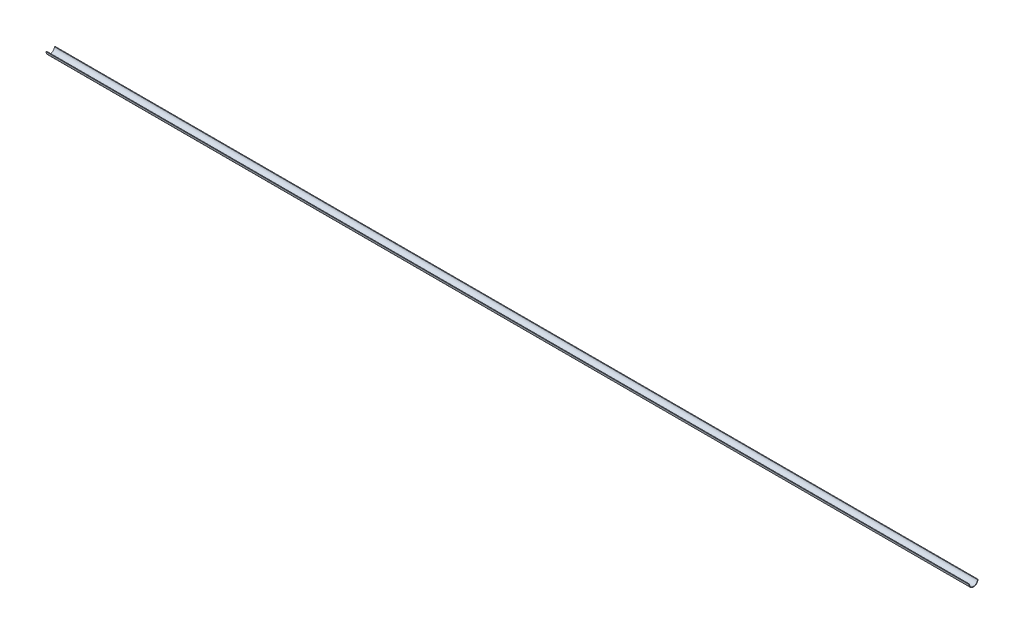
SolidWorks part; units mm, degrees
ref_plane "Plane1" through (0, 0, 0) normal (0, 0, 1) x (1, 0, 0)
ref_plane "Plane2" through (0, 0, 0) normal (0, 1, 0) x (1, 0, 0)
ref_plane "Plane3" through (0, 0, 0) normal (1, 0, 0) x (0, 0, -1)
sketch "HoldingSke" plane through (0, 0, 0) normal (0, 1, 0) x (1, 0, 0)
  line L0 (0, 0) -> (149.0697, -31.6857)
  line L1 (-15, 0) -> (100, 0) construction
  line L2 (0, 0) -> (-2.1039, 2.3779)
  line L3 (0, 0) -> (-11.863, 4.5341)
  line L4 (0, 0) -> (6.9867, 5.0761)
  line L5 (0, 0) -> (-47.5972, -17.7524)
  line L6 (0, 0) -> (-21.0557, -14.2063)
  line L7 (-2.1039, 2.3779) -> (8.8308, 51.9871)
  line L8 (-76.2, 54.61) -> (-16.51, 54.61)
  line L9 (-67.7845, 28.3722) -> (-49.3413, 33.142)
  line L10 (-76.2, 71.12) -> (104.1128, 71.12)
  line L11 (0, 0) -> (-25.4, 0)
  line L12 (-76.2, 101.6) -> (-76.0298, 101.6)
  line L13 (24.9733, 27.94) -> (52.9518, 28.4284)
  line L14 (24.9733, 27.94) -> (24.9746, 27.94)
  line L15 (24.9733, 27.94) -> (100.4006, 29.5858)
  circle A0 centre (0, 0) radius 26.9875
  circle A1 centre (0, 0) radius 0.1086
  circle A2 centre (0, 0) radius 38.1
  circle A3 centre (0, 0) radius 0.1076
  dimension "Num_teeth" = 36
  dimension "H" = 19.05
  dimension "Pitch_radius" = 180.3128
  dimension "Width" = 25.4
  dimension "Thickness" = 25.4
sketch "BasProSke" plane through (0, 0, 0) normal (0, 1, 0) x (1, 0, 0)
  line L0 (-10, 0) -> (60, 0) construction
  line L1 (0, 0) -> (0, 0.1247)
  line L2 (0, 0) -> (25.4, 0)
  line L3 (25.4, 0) -> (25.4, 0.1247)
  line L4 (25.4, 0.1247) -> (0, 0.1247)
  dimension "Thickness" = 25.4
  dimension "Diameter" = 0.2493
revolve "Base-Revolve" add sketch "BasProSke" angle 360 about L0
sketch "TooCutSke"
extrude "ToothCut" cut sketch "TooCutSke" along normal through all rebuild error yes
fillet "Breaks" [suppressed] radius 0.0001 tangent propagation no
fillet "RootFillets" [suppressed] radius 0.0029
pattern_circular "TeethCuts" count 13 every 10 about axis through (-10, 0, 0) along (1, 0, 0) rebuild error yes
sketch "HubNeaOneSke" plane through (0, 0, 0) normal (-1, 0, 0) x (0, 0, 1)
  circle A0 centre (0, 0) radius 0.1086
  dimension "Diameter" = 0.2173
extrude "HubNearOne" [suppressed] add sketch "HubNeaOneSke" along normal blind 25.4
sketch "HubNeaBotSke" plane through (0, 0, 0) normal (-1, 0, 0) x (0, 0, 1)
  circle A0 centre (0, 0) radius 0.1086
  dimension "Diameter" = 0.2173
extrude "HubNearBoth" [suppressed] add sketch "HubNeaBotSke" along normal blind 12.7
ref_plane "FarPln" through (25.4, 0, 0) normal (1, 0, 0) x (0, 0, -1)
sketch "HubFarSke" plane through (25.4, 0, 0) normal (1, 0, 0) x (0, 0, -1)
  circle A0 centre (0, 0) radius 0.1086
  dimension "Diameter" = 0.2173
extrude "HubFar" [suppressed] add sketch "HubFarSke" along normal blind 12.7
sketch "BorSke" plane through (0, 0, 0) normal (1, 0, 0) x (0, 0, -1)
  circle A0 centre (0, 0) radius 0.1076
  dimension "Diameter" = 0.2153
extrude "Bore" cut sketch "BorSke" along normal mid plane 101.6
sketch "KeySke" plane through (0, 0, 0) normal (1, 0, 0) x (0, 0, -1)
  line L0 (-6.35, 0) -> (-6.35, 59.5824)
  line L1 (-6.35, 59.5824) -> (6.35, 59.5824)
  line L2 (6.35, 59.5824) -> (6.35, 0)
  line L3 (0, 0) -> (0, 34) construction
  line L4 (-6.35, 0) -> (6.35, 0)
  dimension "Width" = 12.7
extrude "Keyway" cut sketch "KeySke" along normal mid plane 101.6
pattern_circular "Keyway2" [suppressed] count 2 every 90 about axis through (-10, 0, 0) along (1, 0, 0) reverse direction yes
sketch "Sketch1" plane through (25.4, 0, 0) normal (1, 0, 0) x (0, 0, -1)
  line L0 (0, 0) -> (-61.4073, -35.4535)
  line L1 (-61.4073, -35.4535) -> (-75.2078, -45.2777)
  line L3 (0.9665, 70.9005) -> (4.0387, 87.6924)
  arc A0 (-62.5405, -33.414) -> (-60.2076, -37.4547) centre (0, 0) ccw construction
  circle A1 centre (0, 0) radius 70.9071
  circle A2 centre (0, 0) radius 87.7854
sketch "Sketch3" plane through (25.4, 0, 0) normal (1, 0, 0) x (0, 0, -1)
  line L0 (-61.7691, -34.2346) -> (-76.8798, -41.9429)
  line L1 (0, 70.6217) -> (-2.474, 87.542)
  circle A0 centre (0, 0) radius 70.6217
  circle A1 centre (0, 0) radius 87.5769
extrude "Cut-Extrude2" cut sketch "Sketch3" against normal blind 50.8 contours L0 A1 L1 A0 rebuild error yes
scale "Scale1" scale about centroid uniform scaling yes scale factor 0.39
equation "' \"Pitch@HoldingSke\" = 4"
equation "' \"Num_teeth@HoldingSke\" = 12"
equation "' \"Ap@HoldingSke\" =  20"
equation "' \"Ap@HoldingSke\" = 20"
equation "' \"Width@HoldingSke\" = 0.5"
equation "' \"Hub_dia@HoldingSke\"= 1"
equation "' \"Hub_dia@HoldingSke\" = 1"
equation "' \"Overall_len@HoldingSke\" = 1.0"
equation "' \"Bore@HoldingSke\" = 0.75"
equation "' \"T_dim@HoldingSke\" = 0.85"
equation "' \"Width@KeySke\" = 0.25"
equation "' \"Show_teeth@HoldingSke\" = 13"
equation "' \"Backlash@HoldingSke\" = 0.009"
equation "' \"Addendum_fac@HoldingSke\" = 1.0"
equation "' \"Dedendum_fac@HoldingSke\" = 1.25"
equation "' \"Dedendum_add@HoldingSke\" = 0.00005"
equation "' \"Clearance_fac@HoldingSke\" = 0.25"
equation "' \"Pitch@HoldingSke\" = 0.5"
equation "' \"Num_teeth@HoldingSke\" = 23"
equation "' \"Show_teeth@HoldingSke\" = 23"
equation "' \"Backlash@HoldingSke\" = 0.0375"
equation "\"Overcut_dia@TooCutSke\" = (\"Num_teeth@HoldingSke\" + 2 * \"Addendum_fac@HoldingSke\") / \"Pitch@HoldingSke\" + 0.002"
equation "\"Pitch_dia@TooCutSke\" = \"Num_teeth@HoldingSke\" / \"Pitch@HoldingSke\""
equation "\"Base_dia@TooCutSke\" = \"Num_teeth@HoldingSke\" / \"Pitch@HoldingSke\" * cos((\"Ap@HoldingSke\"  * 3.14159265 / 180))"
equation "\"Root_dia@TooCutSke\" = (\"Num_teeth@HoldingSke\" + 2) / \"Pitch@HoldingSke\" - 2 * (\"Addendum_fac@HoldingSke\" + \"Dedendum_fac@HoldingSke\") / \"Pitch@HoldingSke\" - \"Dedendum_add@HoldingSke\" * 2"
equation "\"Half_ang@TooCutSke\" = 180 / \"Num_teeth@HoldingSke\""
equation "\"Half_CT@TooCutSke\" = \"Num_teeth@HoldingSke\" / \"Pitch@HoldingSke\" * sin((3.14159265 / 2 / \"Num_teeth@HoldingSke\")) / 2 - 7 * \"Backlash@HoldingSke\" / 4"
equation "\"Flank_rad@TooCutSke\" = \"Num_teeth@HoldingSke\" / \"Pitch@HoldingSke\" / 5"
equation "\"Radius@RootFillets\" = \"Clearance_fac@HoldingSke\" / \"Pitch@HoldingSke\" + \"Dedendum_add@HoldingSke\""
equation "\"Break_rad@Breaks\" = 0.02 / \"Pitch@HoldingSke\""
equation "\"Thickness@HoldingSke\" = \"Width@HoldingSke\""
equation "\"OAL@HoldingSke\" = \"Thickness@HoldingSke\""
equation "\"MHD@HoldingSke\" = (\"Num_teeth@HoldingSke\" + 2) / \"Pitch@HoldingSke\" - 2 * (\"Addendum_fac@HoldingSke\" + \"Dedendum_fac@HoldingSke\")  / \"Pitch@HoldingSke\" - \"Dedendum_add@HoldingSke\" * 2"
equation "\"MBD@HoldingSke\" = (\"Num_teeth@HoldingSke\" + 2) / \"Pitch@HoldingSke\" - 2 * (\"Addendum_fac@HoldingSke\" + \"Dedendum_fac@HoldingSke\")  / \"Pitch@HoldingSke\" - \"Dedendum_add@HoldingSke\" * 2 - 0.002"
equation "\"MHD@HoldingSke\" = ((sgn( \"MHD@HoldingSke\" - \"Hub_dia@HoldingSke\" )-1)*( \"MHD@HoldingSke\" - \"Hub_dia@HoldingSke\" ))/-2+ \"Hub_dia@HoldingSke\""
equation "\"MBD@HoldingSke\" = ((sgn( \"MBD@HoldingSke\" - \"Bore@HoldingSke\" )-1)*( \"MBD@HoldingSke\" - \"Bore@HoldingSke\" ))/-2+ \"Bore@HoldingSke\""
equation "\"OAL@HoldingSke\" = ((sgn( \"OAL@HoldingSke\" - \"Overall_len@HoldingSke\" )+1)*( \"OAL@HoldingSke\" - \"Overall_len@HoldingSke\" ))/2 + \"Overall_len@HoldingSke\" + 0.000002"
equation "\"Num_teeth@TeethCuts\" = int( \"Show_teeth@HoldingSke\" ) + 1"
equation "\"Num_teeth@TeethCuts\" = ((sgn( \"Num_teeth@TeethCuts\" - \"Num_teeth@HoldingSke\" )-1)*( \"Num_teeth@TeethCuts\" - \"Num_teeth@HoldingSke\" ))/-2+ \"Num_teeth@HoldingSke\""
equation "\"Num_teeth@TeethCuts\" = ((sgn( \"Num_teeth@TeethCuts\" - 2.0)+1)*( \"Num_teeth@TeethCuts\" - 2.0))/2 +2.0"
equation "\"Angle@TeethCuts\" = 360.0 / \"Num_teeth@HoldingSke\""
equation "\"Diameter@BasProSke\" = (\"Num_teeth@HoldingSke\" + 2 * \"Addendum_fac@HoldingSke\") / \"Pitch@HoldingSke\""
equation "\"Thickness@BasProSke\"  = \"Thickness@HoldingSke\""
equation "' \"Fillet_rad@BasProSke\" =  \"Thickness@HoldingSke\" * 0.05"
equation "' \"Fillet_rad@BasProSke\" = \"Thickness@HoldingSke\" * 0.05"
equation "\"MHD@HoldingSke\" = ((sgn( \"MHD@HoldingSke\" - \"Root_dia@TooCutSke\" )-1)*( \"MHD@HoldingSke\" - \"Root_dia@TooCutSke\" ))/-2+ \"Root_dia@TooCutSke\""
equation "\"Diameter@HubNeaOneSke\" = \"MHD@HoldingSke\""
equation "\"Length@HubNearOne\" = \"OAL@HoldingSke\" - \"Thickness@BasProSke\""
equation "\"Diameter@HubNeaBotSke\" = \"MHD@HoldingSke\""
equation "\"Length@HubNearBoth\" = ( \"OAL@HoldingSke\" - \"Thickness@BasProSke\" ) / 2.0"
equation "\"Thickness@FarPln\" = \"Thickness@BasProSke\""
equation "\"Diameter@HubFarSke\" = \"MHD@HoldingSke\""
equation "\"Length@HubFar\" = ( \"OAL@HoldingSke\" - \"Thickness@BasProSke\" ) / 2.0"
equation "\"Diameter@BorSke\" = \"MBD@HoldingSke\""
equation "\"D1@Bore\" = \"OAL@HoldingSke\" * 2.0"
equation "\"D1@Keyway\" = \"OAL@HoldingSke\" * 2.0"
equation "\"Offset@KeySke\" = \"T_dim@HoldingSke\" - \"MBD@HoldingSke\" / 2.0"
